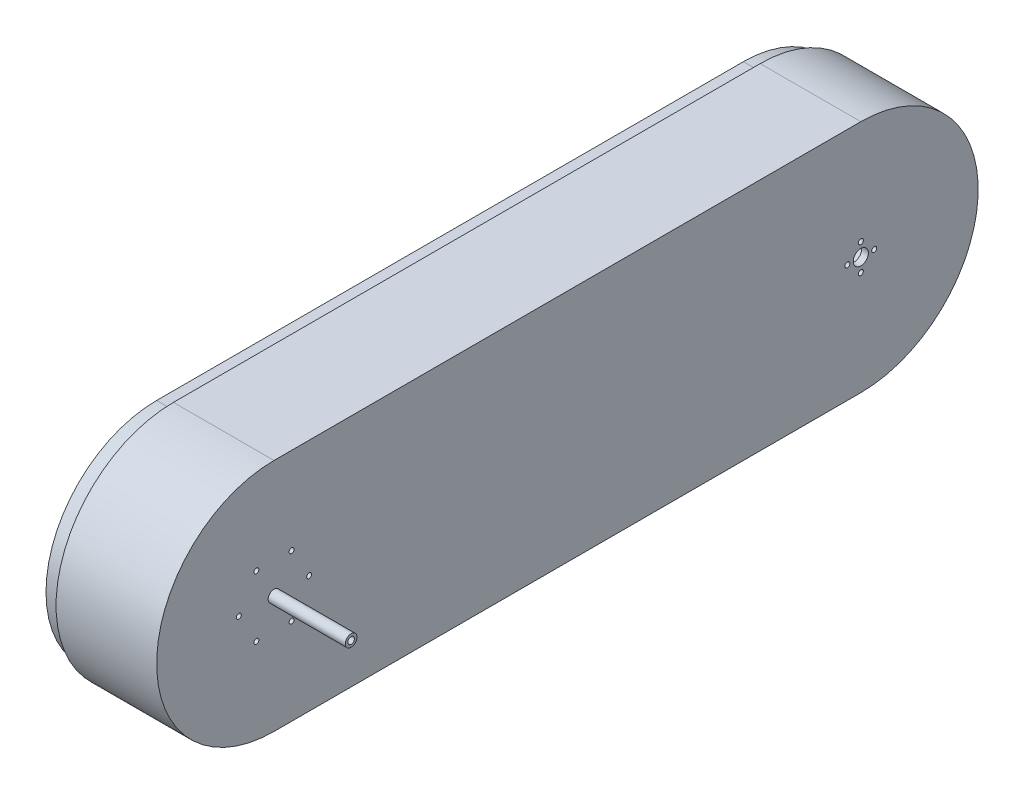
SolidWorks part; units mm, degrees
material "Cast Alloy Steel"
ref_plane "Front Plane" through (0, 0, 0) normal (0, 0, 1) x (1, 0, 0)
ref_plane "Top Plane" through (0, 0, 0) normal (0, 1, 0) x (1, 0, 0)
ref_plane "Right Plane" through (0, 0, 0) normal (1, 0, 0) x (0, 0, -1)
sketch "Sketch2" plane through (0, 0, 0) normal (1, 0, 0) x (0, 0, -1)
  line L0 (-107.709, -46.1404) -> (242.291, -46.1404)
  line L1 (242.291, -46.1404) -> (242.291, 93.8596)
  line L2 (242.291, 93.8596) -> (-107.709, 93.8596)
  line L3 (-107.709, 93.8596) -> (-107.709, -46.1404)
  circle A0 centre (-107.709, 23.8596) radius 70
  circle A1 centre (242.291, 23.8596) radius 70
  point P9 (-107.709, 23.8596)
  dimension "D1" = 350
  dimension "D2" = 140
extrude "Boss-Extrude1" add sketch "Sketch2" along normal blind 60 contours A1 L2 A0 L0 | L3 A0 | L3 A0 | L1 A1 | L1 A1 region at (0, 23.8596, -67.291) region at (0, 23.8596, 137.4179) region at (0, 23.8596, 78.0001) region at (0, 23.8596, -212.5821) region at (0, 23.8596, -271.9999)
shell "Shell1" thickness 4 removed face at (0, 23.8596, -67.291)
sketch "Sketch4" plane through (56, 0, 0) normal (-1, 0, 0) x (0, 0, 1)
  line L1 (-242.291, 23.8596) -> (-242.291, 31.8596)
  line L2 (-242.291, 23.8596) -> (-234.291, 23.8596)
  line L3 (-242.291, 23.8596) -> (-242.291, 15.8596)
  line L5 (-242.291, 23.8596) -> (-250.291, 23.8596)
  circle A0 centre (-242.291, 23.8596) radius 8
  circle A2 centre (-242.291, 31.8596) radius 1.5
  circle A3 centre (-250.291, 23.8596) radius 1.5
  circle A4 centre (-234.291, 23.8596) radius 1.5
  circle A6 centre (-242.291, 15.8596) radius 1.5
  dimension "D1" = 16
  dimension "D6" = 3
  dimension "D7" = 3
  dimension "D8" = 3
  dimension "D10" = 3
  dimension "D2" = 180
  dimension "D3" = 90
extrude "Cut-Extrude1" cut sketch "Sketch4" against normal blind 40 contours A2 | A4 | A6 | A3
sketch "Sketch6" plane through (56, 0, 0) normal (-1, 0, 0) x (0, 0, 1)
  circle A0 centre (-242.291, 23.8596) radius 4.5
  dimension "D1" = 9
extrude "Cut-Extrude2" cut sketch "Sketch6" against normal blind 40
sketch "Sketch7" plane through (56, 0, 0) normal (-1, 0, 0) x (0, 0, 1)
  circle A1 centre (86.709, 23.8596) radius 1.5
  circle A2 centre (97.209, 42.0462) radius 1.5
  circle A3 centre (107.709, 23.8596) radius 21 construction
  circle A4 centre (118.209, 42.0462) radius 1.5
  circle A5 centre (107.709, 23.8596) radius 21 construction
  circle A6 centre (128.709, 23.8596) radius 1.5
  circle A7 centre (107.709, 23.8596) radius 21 construction
  circle A8 centre (118.209, 5.6731) radius 1.5
  circle A9 centre (107.709, 23.8596) radius 21 construction
  circle A10 centre (97.209, 5.6731) radius 1.5
  circle A11 centre (107.709, 23.8596) radius 21 construction
  point P24 (107.709, 23.8596)
  dimension "D1" = 3
  dimension "D4" = 42
  dimension "D3" = 21
  dimension "D2" = 6
extrude "Cut-Extrude3" cut sketch "Sketch7" against normal blind 10
sketch "Sketch8" plane through (56, 0, 0) normal (-1, 0, 0) x (0, 0, 1)
  circle A0 centre (107.709, 23.8596) radius 3.5
  dimension "D1" = 7
extrude "Boss-Extrude2" add sketch "Sketch8" against normal blind 50
sketch "Sketch9" plane through (56, 0, 0) normal (-1, 0, 0) x (0, 0, 1)
  line L0 (-152.291, -32.1404) -> (-155.291, -32.1404)
  line L1 (-152.291, -32.1404) -> (-152.291, 11.4197)
  line L2 (-155.291, -32.1404) -> (-155.291, 11.4197)
  line L3 (-152.291, 11.4197) -> (-155.291, 11.4197)
extrude "Boss-Extrude3" add sketch "Sketch9" along normal blind 50
sketch "Sketch10" plane through (0, 0, -152.291) normal (0, 0, 1) x (1, 0, 0)
  line L0 (6, -32.1404) -> (56, -32.1404) construction
  line L1 (6, -32.1404) -> (6, 11.4197) construction
  circle A0 centre (31, -12.1404) radius 5
  circle A1 centre (31, -12.1404) radius 15.7942
  dimension "D1" = 10
  dimension "D2" = 31.5883
  dimension "D4" = 25
  dimension "D3" = 20
extrude "Cut-Extrude4" cut sketch "Sketch10" against normal blind 30 contours A0 region at (31, -12.1404, -152.291)
sketch "Sketch11" plane through (0, 0, 0) normal (-1, 0, 0) x (0, 0, 1)
  line L0 (107.709, 93.8596) -> (-242.291, 93.8596)
  line L1 (-242.291, 93.8596) -> (-242.291, -46.1404)
  line L2 (-242.291, -46.1404) -> (107.709, -46.1404)
  circle A0 centre (107.709, 23.8596) radius 70
  circle A3 centre (-242.291, 23.8596) radius 70
  arc M1 (107.709, 89.8596) -> (107.709, -42.1404) centre (107.709, 23.8596) cw
  line M2 (107.709, -42.1404) -> (-242.291, -42.1404)
  arc M3 (-242.291, -42.1404) -> (-242.291, 89.8596) centre (-242.291, 23.8596) cw
  line M4 (-242.291, 89.8596) -> (107.709, 89.8596)
extrude "Boss-Extrude4" add sketch "Sketch11" along normal blind 10 separate body contours A0 M4 M2 M1 | A3 A0 M2 M4 | A3 L1 M2 M4 | L1 M3 region at (0, 23.8596, 105.2181) region at (0, 23.8596, -67.291) region at (0, 23.8596, -212.2363) region at (0, 23.8596, -270.3023)
sketch "Sketch12" plane through (106, 0, 0) normal (1, 0, 0) x (0, 0, -1)
  point P0 (-107.709, 23.8596)
sketch "Sketch13" plane through (106, 0, 0) normal (1, 0, 0) x (0, 0, -1)
  circle A0 centre (-107.709, 23.8596) radius 2
extrude "Cut-Extrude5" cut sketch "Sketch13" against normal blind 65 contours A0
sketch "Sketch17" plane through (0, -46.1404, 0) normal (0, -1, 0) x (-1, 0, 0)
  line L1 (-23.4131, -88.4087) -> (-33.8351, -88.4087)
  line L2 (-23.4131, -88.4087) -> (-23.4131, 135.6635)
  line L3 (-23.4131, 135.6635) -> (-33.8351, 135.6635)
  line L4 (-33.8351, -88.4087) -> (-33.8351, 135.6635)
extrude "Boss-Extrude5" add sketch "Sketch17" against normal blind 9
sketch "Sketch18" plane through (0, 0, -135.6635) normal (0, 0, -1) x (-1, 0, 0)
  circle A0 centre (-28.5662, -39.6404) radius 1.9376
extrude "Cut-Extrude6" cut sketch "Sketch18" against normal blind 239
